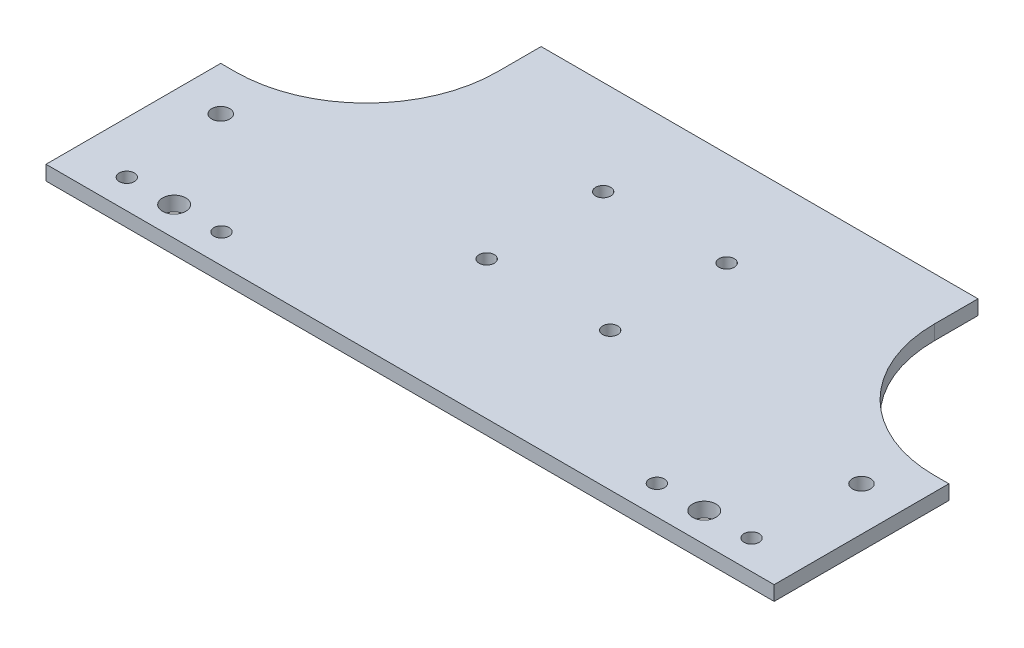
SolidWorks part; units mm, degrees
ref_plane "Front Plane" through (0, 0, 0) normal (0, 0, 1) x (1, 0, 0)
ref_plane "Top Plane" through (0, 0, 0) normal (0, 1, 0) x (1, 0, 0)
ref_plane "Right Plane" through (0, 0, 0) normal (1, 0, 0) x (0, 0, -1)
sketch "Sketch1" plane through (0, 0, 0) normal (0, 1, 0) x (1, 0, 0)
  line L0 (0, 0) -> (0, 64.2675) construction
  line L1 (-125, -45) -> (125, -45)
  line L2 (-125, -45) -> (-125, 15)
  line L3 (-125, 15) -> (125, 15) construction
  line L4 (125, -45) -> (125, 15)
  line L5 (0, 15) -> (0, -45) construction
  line L6 (-75, 60) -> (-75, 75)
  line L7 (-75, 75) -> (0, 75)
  line L8 (-125, 15) -> (-120, 15)
  line L9 (0, 75) -> (75, 75)
  line L10 (75, 75) -> (75, 60)
  line L11 (120, 15) -> (125, 15)
  circle A0 centre (-91, -35) radius 4
  circle A1 centre (91, -35) radius 4
  arc A2 (75, 60) -> (120, 15) centre (120, 60) ccw
  arc A3 (-75, 60) -> (-120, 15) centre (-120, 60) cw
  point P0 (0, 0)
  point P23 (-75, 15)
  dimension "D6" = 8
  dimension "D7" = 60
  dimension "D10" = 45
  dimension "D1" = 250
  dimension "D2" = 60
  dimension "D3" = 91
  dimension "D4" = 125
  dimension "D5" = 10
  dimension "D8" = 75
  dimension "D9" = 75
extrude "Boss-Extrude1" add sketch "Sketch1" along normal blind 5
sketch "Sketch2" plane through (0, 0, 0) normal (0, -1, 0) x (1, 0, 0)
  circle A0 centre (110, 0) radius 3.1
  circle A1 centre (74.75, 35) radius 2.6
  circle A2 centre (107.25, 35) radius 2.6
  circle A3 centre (-110, 0) radius 3.1
  circle A4 centre (-74.75, 35) radius 2.6
  circle A5 centre (-107.25, 35) radius 2.6
  circle A6 centre (-21.2, -2.5) radius 2.6
  circle A7 centre (21.2, -2.5) radius 2.6
  circle A8 centre (-21.2, -42.5) radius 2.6
  circle A9 centre (21.2, -42.5) radius 2.6
  dimension "D1" = 5.2
  dimension "D2" = 6.2
  dimension "D3" = 6.2
  dimension "D4" = 5.2
  dimension "D5" = 5.2
  dimension "D6" = 5.2
  dimension "D7" = 5.2
  dimension "D8" = 5.2
  dimension "D9" = 5.2
  dimension "D10" = 5.2
extrude "Cut-Extrude1" cut sketch "Sketch2" against normal blind 10
